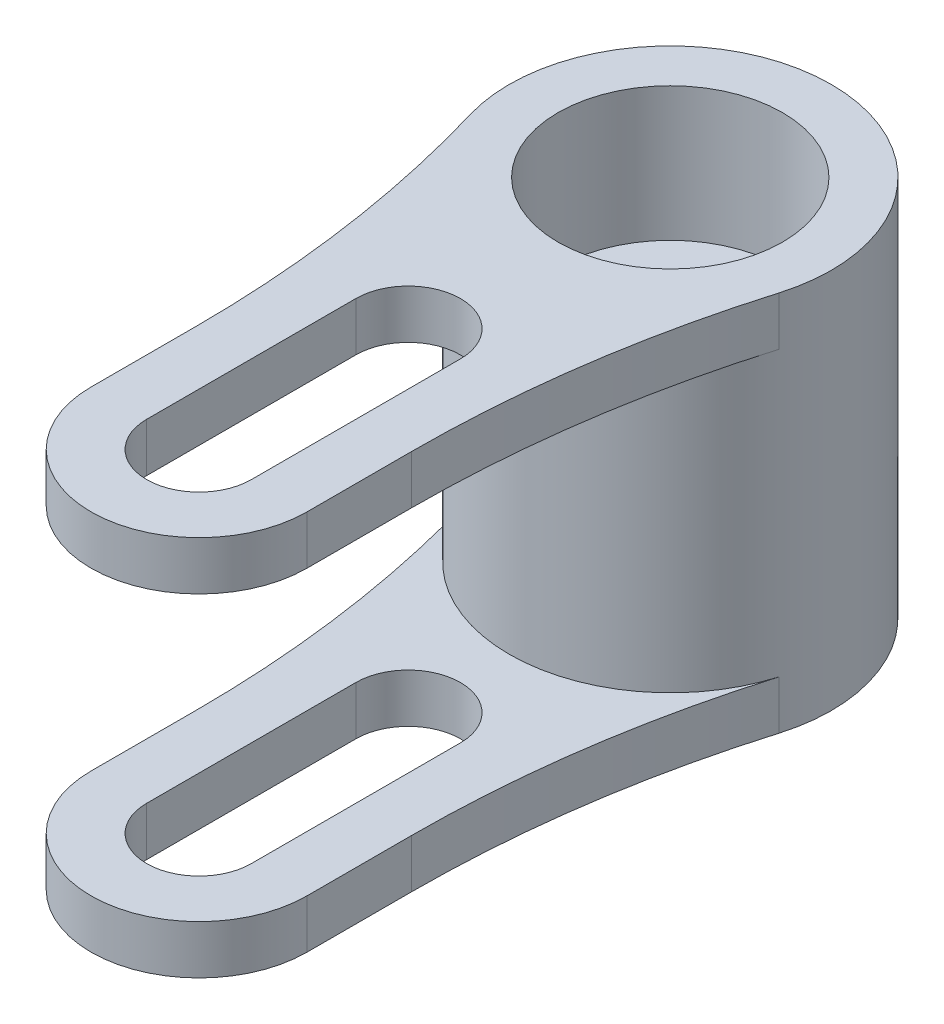
SolidWorks part; units mm, degrees
ref_plane "Front Plane" through (0, 0, 0) normal (0, 0, 1) x (1, 0, 0)
ref_plane "Top Plane" through (0, 0, 0) normal (0, 1, 0) x (1, 0, 0)
ref_plane "Right Plane" through (0, 0, 0) normal (1, 0, 0) x (0, 0, -1)
sketch "Sketch1" plane through (0, 0, 0) normal (0, 1, 0) x (1, 0, 0)
  line L0 (0, 5.775) -> (0, 4.025) construction
  line L1 (0, -9.4) -> (0, -16.9) construction
  line L2 (-3.875, -13.15) -> (-3.875, -16.9)
  line L3 (3.875, -16.9) -> (3.875, -13.15)
  line L4 (1.875, -9.4) -> (1.875, -16.9)
  line L5 (-1.875, -9.4) -> (-1.875, -16.9)
  line L6 (0, -7.525) -> (0, -5.775) construction
  line L7 (-3.875, -13.15) -> (3.875, -13.15) construction
  circle A0 centre (0, 0) radius 4.025
  circle A1 centre (0, 0) radius 5.775
  arc A2 (1.875, -9.4) -> (-1.875, -9.4) centre (0, -9.4) ccw
  arc A3 (-5.5388, -1.6347) -> (-3.875, -13.15) centre (-44.5559, -13.15) cw
  arc A4 (-3.875, -16.9) -> (3.875, -16.9) centre (0, -16.9) ccw
  arc A5 (3.875, -13.15) -> (5.5388, -1.6347) centre (44.5559, -13.15) cw
  arc A6 (-1.875, -16.9) -> (1.875, -16.9) centre (0, -16.9) ccw
  point P6 (0, -13.15)
  point P20 (0, 0)
  dimension "D1" = 8.05
  dimension "D2" = 1.75
  dimension "D3" = 3.75
  dimension "D4" = 2
  dimension "D5" = 7.5
  dimension "D6" = 1.75
extrude "Boss-Extrude1" add sketch "Sketch1" along normal mid plane 13.675 contours L3 A5 A1 A3 L2 A4 A6 L5 A2 L4 | A0 | A1 A0 region at (-4.0742, 0, 7.3009) region at (-0.8025, 0, -5.554) region at (0, 0, 0)
ref_plane "Plane1" through (0, -5.0875, 0) normal (0, -1, 0) x (-1, 0, 0)
ref_plane "Plane2" through (0, 5.0875, 0) normal (0, 1, 0) x (1, 0, 0)
extrude "Cut-Extrude1" cut sketch "Sketch1<4>" along normal up to surface (10.175 mm away) from surface contours L3 A5 A1 A3 L2 A4 A6 L5 A2 L4 region at (-4.0742, 0, 7.3009) up to plane "Plane2" starting at plane "Plane1"
sketch "Sketch1<4>" plane through (0, 0, 0) normal (0, 1, 0) x (1, 0, 0) same geometry as "Sketch1"
extrude "Cut-Extrude2" cut sketch "Sketch1<5>" against normal blind 4.8 from surface contours A0 region at (0, 0, 0) starting at face at (0, 6.8375, 13.15)
sketch "Sketch1<5>" plane through (0, 0, 0) normal (0, 1, 0) x (1, 0, 0) same geometry as "Sketch1"
equation "\"D1@Boss-Extrude1\"=9.525mm+1.75mm+1.75mm+.65mm"
